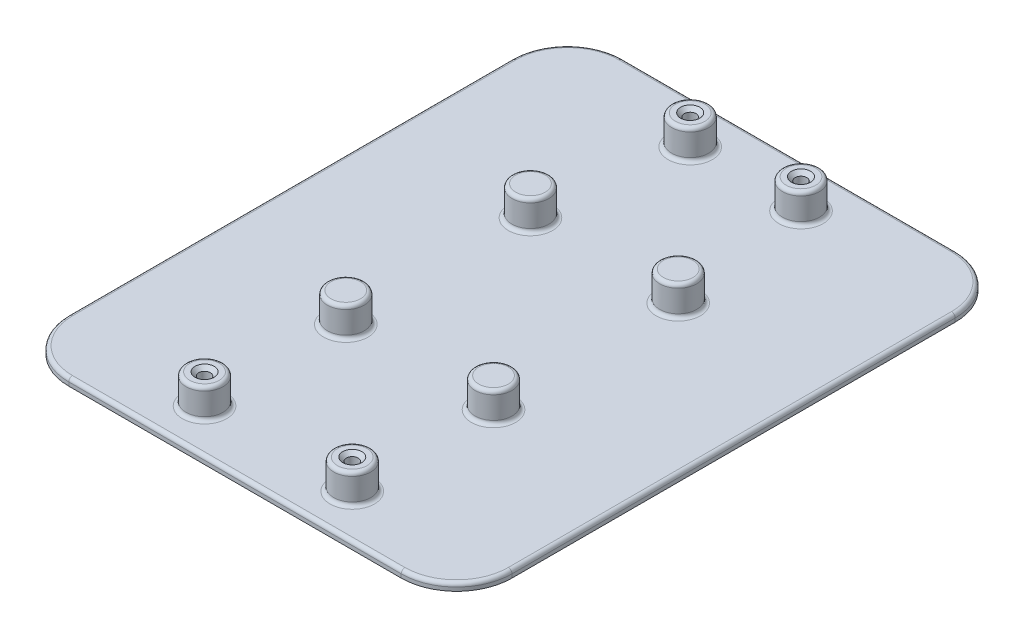
SolidWorks part; units mm, degrees
ref_plane "Front Plane" through (0, 0, 0) normal (0, 0, 1) x (1, 0, 0)
ref_plane "Top Plane" through (0, 0, 0) normal (0, 1, 0) x (1, 0, 0)
ref_plane "Right Plane" through (0, 0, 0) normal (1, 0, 0) x (0, 0, -1)
sketch "Sketch1" plane through (0, 0, 0) normal (0, 1, 0) x (1, 0, 0)
  line L1 (15, 0) -> (105, 0)
  line L2 (0, 15) -> (0, 135)
  line L3 (15, 150) -> (105, 150)
  line L4 (120, 15) -> (120, 135)
  arc A0 (15, 0) -> (0, 15) centre (15, 15) cw
  arc A1 (105, 0) -> (120, 15) centre (105, 15) ccw
  arc A2 (105, 150) -> (120, 135) centre (105, 135) cw
  arc A3 (0, 135) -> (15, 150) centre (15, 135) cw
  point P7 (0, 0)
  point P12 (120, 150)
  point P15 (0, 150)
  dimension "D3" = 15
  dimension "D1" = 150
  dimension "D2" = 120
extrude "Boss-Extrude1" add sketch "Sketch1" along normal blind 2
sketch "Sketch2" plane through (0, 2, 0) normal (0, 1, 0) x (1, 0, 0)
  line L0 (60, 0) -> (60, 150) construction
  line L1 (15, 0) -> (105, 0) construction
  line L2 (105, 150) -> (15, 150) construction
  line L3 (120, 75) -> (0, 75) construction
  line L4 (120, 15) -> (120, 135) construction
  line L5 (0, 135) -> (0, 15) construction
  circle A0 centre (45, 138.25) radius 1.5875
  circle A1 centre (75, 138.25) radius 1.5875
  circle A2 centre (80, 11.75) radius 1.5875
  circle A3 centre (40, 11.75) radius 1.5875
  circle A4 centre (45, 138.25) radius 5
  circle A5 centre (75, 138.25) radius 5
  circle A6 centre (40, 11.75) radius 5
  circle A7 centre (80, 11.75) radius 5
  circle A8 centre (40, 50) radius 5
  circle A9 centre (80, 50) radius 5
  circle A10 centre (40, 100) radius 5
  circle A11 centre (80, 100) radius 5
  dimension "D1" = 3.175
  dimension "D2" = 30
  dimension "D4" = 40
  dimension "D6" = 126.5
  dimension "D8" = 10
  dimension "D9" = 10
  dimension "D12" = 20
  dimension "D13" = 25
  dimension "D3" = 15
  dimension "D5" = 20
  dimension "D7" = 63.25
  dimension "D10" = 40
  dimension "D11" = 50
extrude "Boss-Extrude2" add sketch "Sketch2" along normal blind 8
fillet "Fillet1" radius 1 24 edges at (0, 2, -75) (4.3934, 2, -145.6066) (60, 2, -150) (115.6066, 2, -145.6066) (120, 2, -75) (115.6066, 2, -4.3934) (60, 2, 0) (75, 10, -133.25) (45, 10, -133.25) (80, 10, -6.75) (40, 10, -6.75) (4.3934, 2, -4.3934) (80, 2, -16.75) (40, 2, -16.75) (75, 2, -143.25) (45, 2, -143.25) (80, 10, -95) (40, 10, -45) (80, 10, -45) (40, 10, -95) (80, 2, -55) (40, 2, -105) (40, 2, -55) (80, 2, -105)
chamfer "Chamfer1" distance 1 angle 45 4 edges at (80, 10, -10.1625) (40, 10, -10.1625) (75, 10, -136.6625) (45, 10, -136.6625)
